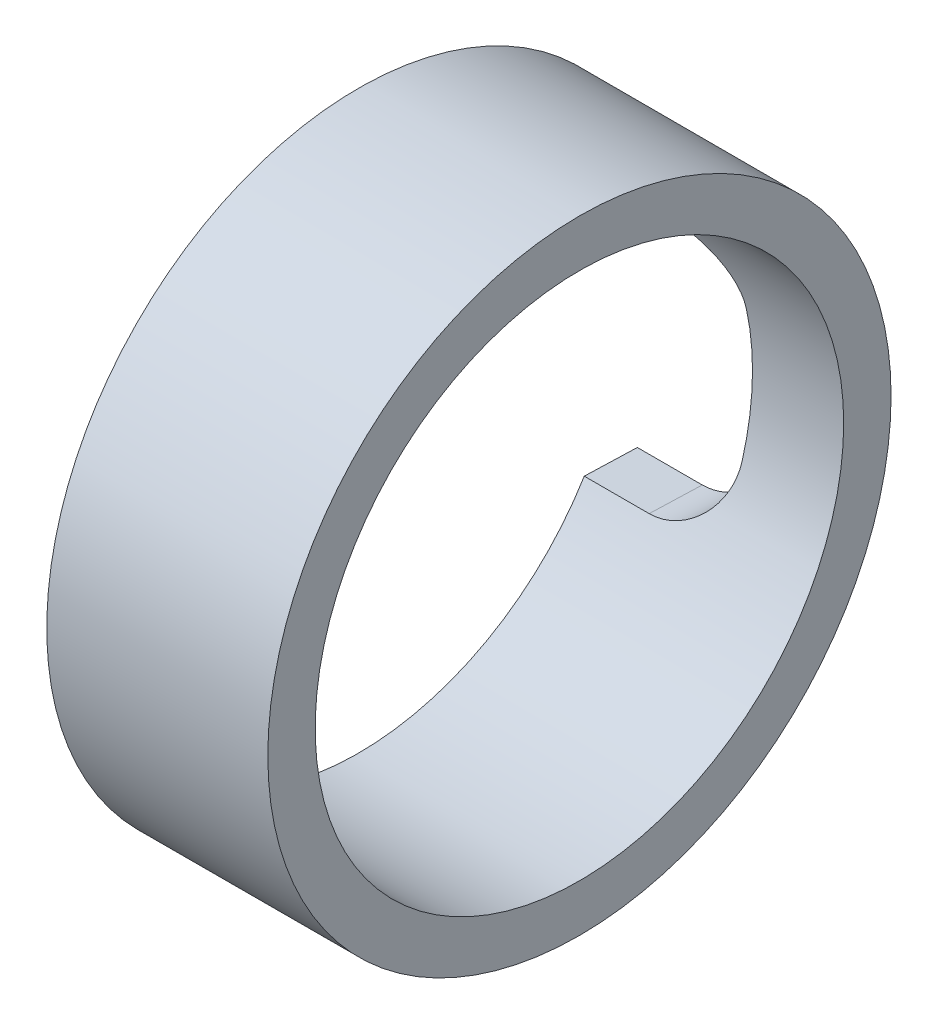
SolidWorks part; units mm, degrees
material "Nylon 6/10"
ref_plane "Front Plane" through (0, 0, 0) normal (0, 0, 1) x (1, 0, 0)
ref_plane "Top Plane" through (0, 0, 0) normal (0, 1, 0) x (1, 0, 0)
ref_plane "Right Plane" through (0, 0, 0) normal (1, 0, 0) x (0, 0, -1)
sketch "Sketch1" plane through (0, 0, 0) normal (0, 0, 1) x (1, 0, 0)
  line L0 (-25.4, 7.5) -> (-42.315, 7.5) construction
  line L1 (-39.013, 9.144) -> (-32.527, 9.144)
  line L2 (-39.013, 9.144) -> (-39.013, 7.754)
  line L3 (-39.013, 7.754) -> (-32.527, 7.754)
  line L4 (-32.527, 9.144) -> (-32.527, 7.754)
  line L5 (-39.14, 7.64) -> (-39.14, 12.4407) construction
  line L6 (-32.4, 15.2446) -> (-32.4, -15.2446) construction
  line L7 (0, 0) -> (-47.1489, 0) construction
  dimension "D1" = 0.254
  dimension "D2" = 0.127
  dimension "D3" = 0.127
  dimension "D4" = 18.288
revolve "Revolve1" add sketch "Sketch1" angle 360 about L7
ref_plane "Plane1" through (0, 0, 0) normal (0, -0.0323, -0.9995) x (1, 0, 0)
sketch "Sketch3" plane through (0, 0, 0) normal (0, -0.0323, -0.9995) x (1, 0, 0)
  line L0 (-39.013, 3.81) -> (-39.013, -3.81)
  line L1 (-39.013, 7.754) -> (-39.013, -7.754) construction
  line L2 (-39.013, -3.81) -> (-37.108, -3.81)
  line L3 (-35.203, -1.905) -> (-35.203, 1.905)
  line L4 (-37.108, 3.81) -> (-39.013, 3.81)
  line L5 (-39.013, 9.144) -> (-39.013, -9.144) construction
  line L6 (-39.013, 9.144) -> (-39.013, -9.144) construction
  line L7 (-35.203, 0) -> (-39.013, 0) construction
  arc A0 (-37.108, -3.81) -> (-35.203, -1.905) centre (-37.108, -1.905) ccw
  arc A1 (-35.203, 1.905) -> (-37.108, 3.81) centre (-37.108, 1.905) ccw
  dimension "D1" = 7.62
  dimension "D2" = 3.81
extrude "Cut-Extrude1" cut sketch "Sketch3" along normal up to next
